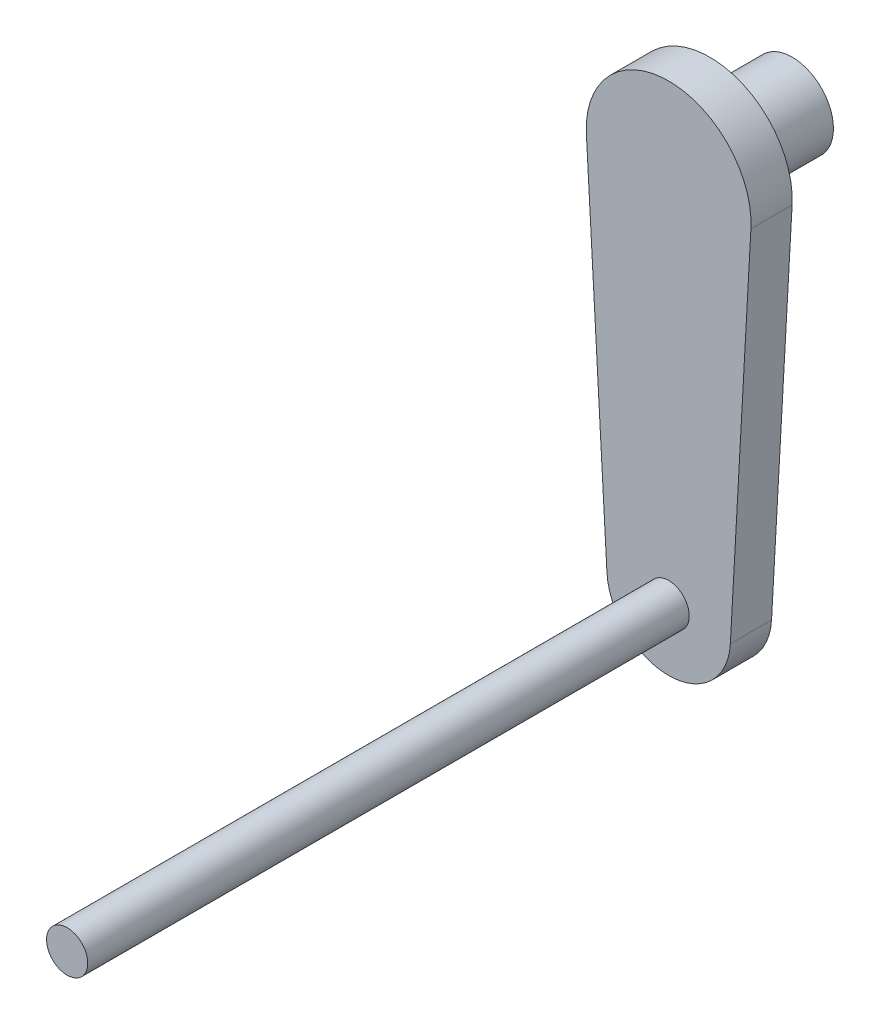
SolidWorks part; units mm, degrees
ref_plane "Front Plane" through (0, 0, 0) normal (0, 0, 1) x (1, 0, 0)
ref_plane "Top Plane" through (0, 0, 0) normal (0, 1, 0) x (1, 0, 0)
ref_plane "Right Plane" through (0, 0, 0) normal (1, 0, 0) x (0, 0, -1)
sketch "Sketch1" plane through (0, 0, 0) normal (0, 0, 1) x (1, 0, 0)
  line L0 (0, 0) -> (0, -57.15) construction
  line L1 (12.6804, -0.7056) -> (9.5103, -57.6792)
  line L2 (-12.6804, -0.7056) -> (-9.5103, -57.6792)
  circle A1 centre (0, 0) radius 6.35
  circle A2 centre (0, 0) radius 57.15 construction
  circle A3 centre (0, -57.15) radius 3.175
  arc A4 (12.6804, -0.7056) -> (-12.6804, -0.7056) centre (0, 0) ccw
  arc A5 (-9.4919, -56.3562) -> (9.4919, -56.3562) centre (0, -57.15) ccw
  arc A6 (0, -12.7) -> (12.6804, -0.7056) centre (0, 0) ccw construction
  circle A7 centre (0, 0) radius 12.7 construction
  arc A8 (-12.6804, -0.7056) -> (0, -12.7) centre (0, 0) ccw construction
  arc A9 (9.4919, -56.3562) -> (0, -47.625) centre (0, -57.15) ccw construction
  circle A10 centre (0, -57.15) radius 9.525 construction
  arc A11 (0, -47.625) -> (-9.4919, -56.3562) centre (0, -57.15) ccw construction
  dimension "D1" = 114.3
  dimension "D2" = 6.35
  dimension "D4" = 12.7
  dimension "D3" = 6.35
extrude "Boss-Extrude1" add sketch "Sketch1" against normal up to surface (12.7 mm away) contours A1
extrude "Boss-Extrude2" add sketch "Sketch1<3>" along normal blind 6.35 contours A1 | L2 A5 L1 A4 A1 A3 region at (0, -26.606, 0) region at (0, 0, 0)
sketch "Sketch1<3>" plane through (0, 0, 0) normal (0, 0, 1) x (1, 0, 0) same geometry as "Sketch1"
extrude "Boss-Extrude3" add sketch "Sketch1<4>" along normal offset from surface (99.06 mm away) 2.54 contours A3
sketch "Sketch1<4>" plane through (0, 0, 0) normal (0, 0, 1) x (1, 0, 0) same geometry as "Sketch1"
ref_point "Point1"
equation "\"D1@Sketch1\"=\"MaxSpinnerDiameter@ConceptAssem_2.Assembly\""
